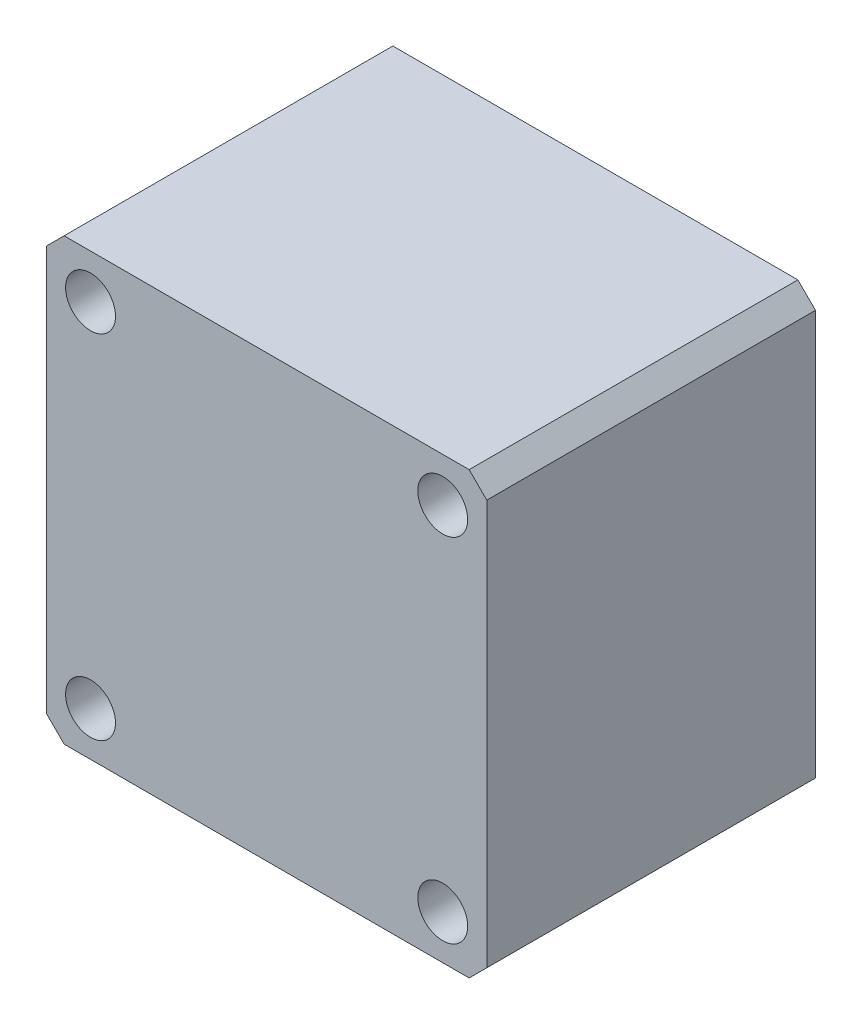
SolidWorks part; units mm, degrees
ref_plane "前视基准面" through (0, 0, 0) normal (0, 0, 1) x (1, 0, 0)
ref_plane "上视基准面" through (0, 0, 0) normal (0, 1, 0) x (1, 0, 0)
ref_plane "右视基准面" through (0, 0, 0) normal (1, 0, 0) x (0, 0, -1)
other "Configuration Table"
sketch "草图1" plane through (0, 0, 0) normal (0, 0, 1) x (1, 0, 0)
  line L1 (0, 0) -> (75, 0)
  line L2 (0, 0) -> (0, -75)
  line L3 (0, -75) -> (75, -75)
  line L4 (75, 0) -> (75, -75)
  dimension "D1" = 75
  dimension "D2" = 75
extrude "凸台-拉伸1" add sketch "草图1" along normal blind 56
chamfer "倒角1" distance 3 angle 45 4 edges at (75, -75, 28) (75, 0, 28) (0, -75, 28) (0, 0, 28)
sketch "草图2" plane through (0, 0, 56) normal (0, 0, 1) x (1, 0, 0)
  line L0 (72, 0) -> (3, 0) construction
  line L1 (0, -3) -> (0, -72) construction
  circle A0 centre (7.5, -7.5) radius 4.25
  circle A4 centre (67.5, -7.5) radius 4.25
  circle A5 centre (67.5, -67.5) radius 4.25
  circle A6 centre (7.5, -67.5) radius 4.25
  dimension "D3" = 8.5
  dimension "D1" = 7.5
  dimension "D2" = 7.5
  dimension "D4" = 2
  dimension "D5" = 2
extrude "切除-拉伸1" cut sketch "草图2" against normal through all
sketch "草图3" plane through (0, 0, 56) normal (0, 0, 1) x (1, 0, 0)
  line L0 (0, -37.5) -> (75, -37.5) construction
  line L1 (0, -3) -> (0, -72) construction
  line L2 (75, -72) -> (75, -3) construction
  line L3 (37.5, 0) -> (37.5, -75) construction
  line L4 (72, 0) -> (3, 0) construction
  line L5 (3, -75) -> (72, -75) construction
